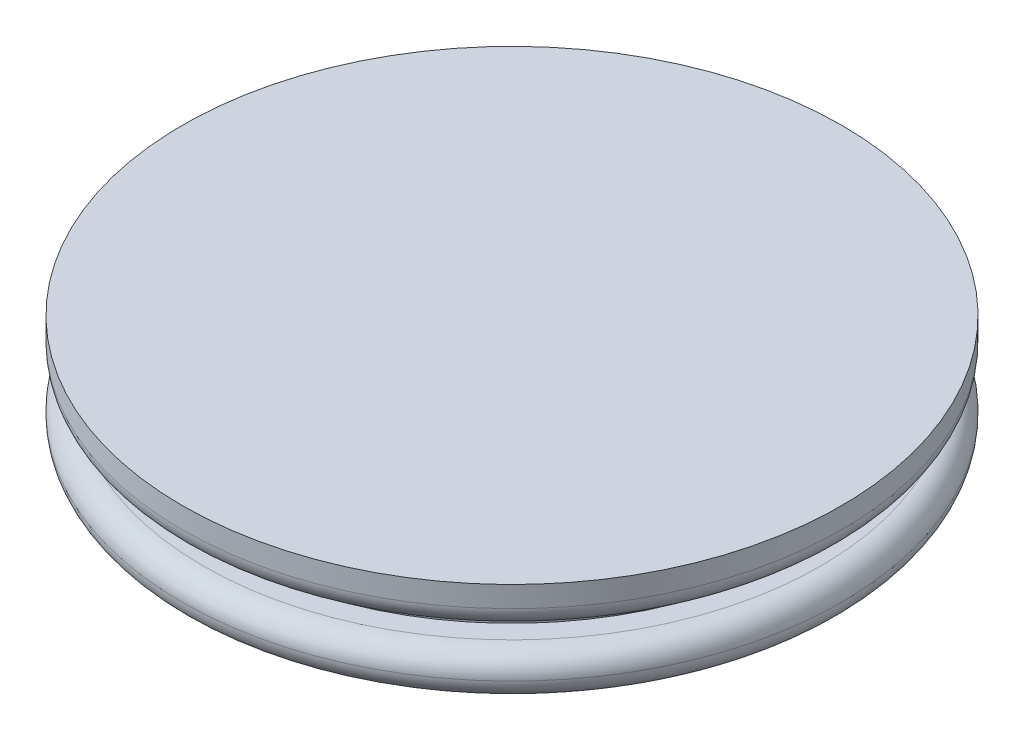
SolidWorks part; units mm, degrees
ref_plane "Front Plane" through (0, 0, 0) normal (0, 0, 1) x (1, 0, 0)
ref_plane "Top Plane" through (0, 0, 0) normal (0, 1, 0) x (1, 0, 0)
ref_plane "Right Plane" through (0, 0, 0) normal (1, 0, 0) x (0, 0, -1)
sketch "Sketch1" plane through (0, 0, 0) normal (0, 1, 0) x (1, 0, 0)
  circle A0 centre (0, 0) radius 20
  point P3 (0, 0)
  dimension "D1" = 40
extrude "Boss-Extrude1" add sketch "Sketch1" along normal blind 2.54 contours A0
sketch "Sketch2" plane through (0, 2.54, 0) normal (0, 1, 0) x (1, 0, 0)
  circle A0 centre (0, 0) radius 17.5
  dimension "D1" = 35
extrude "Boss-Extrude2" add sketch "Sketch2" along normal blind 1.27
sketch "Sketch3" plane through (0, 3.81, 0) normal (0, 1, 0) x (1, 0, 0)
  circle A0 centre (0, 0) radius 20
  dimension "D1" = 40
extrude "Boss-Extrude3" add sketch "Sketch3" along normal blind 2.54 contours A0
fillet "Fillet1" radius 1.27 1 edges at (0, 3.81, 20)
fillet "Fillet2" radius 1.27 2 edges at (0, 0, 20) (0, 2.54, 20)
